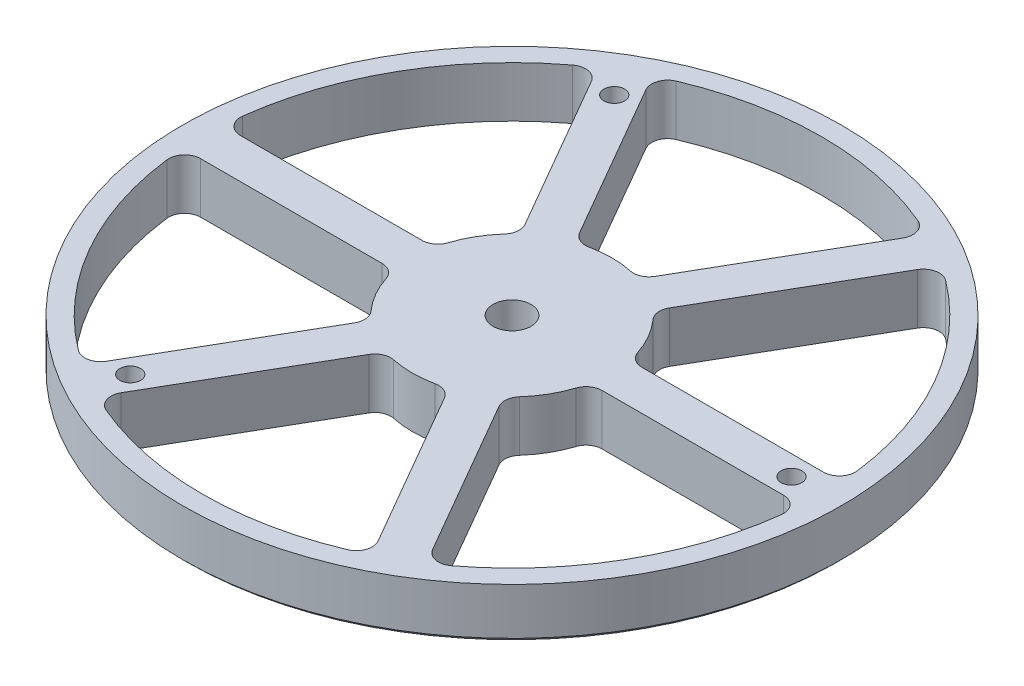
SolidWorks part; units mm, degrees
material "6061-T6 (SS)"
ref_plane "Front Plane" through (0, 0, 0) normal (0, 0, 1) x (1, 0, 0)
ref_plane "Top Plane" through (0, 0, 0) normal (0, 1, 0) x (1, 0, 0)
ref_plane "Right Plane" through (0, 0, 0) normal (1, 0, 0) x (0, 0, -1)
sketch "Sketch2" plane through (0, 0, 0) normal (1, 0, 0) x (0, 0, -1)
  line L0 (0, 0) -> (-82.55, 0)
  line L1 (-82.55, 0) -> (-82.55, 12.7)
  line L2 (-82.55, 12.7) -> (0, 12.7)
  line L5 (0, 12.7) -> (0, 0)
  dimension "D1" = 82.55
  dimension "D2" = 12.7
ref_axis "Axis1" through (0, -0.635, 0) along (0, 1, 0)
revolve "Revolve1" add sketch "Sketch2" angle 360 about axis through (0, -0.635, 0) along (0, 1, 0)
hole_wizard "#6 (0.204) Diameter Hole1" positions "Sketch6" profile "Sketch7" hole size "#6" standard "ANSI Inch" end condition through all
sketch "Sketch6" plane through (0, 12.7, 0) normal (0, 1, 0) x (1, 0, 0)
  line L0 (0, 0) -> (-69.8201, 120.932) construction
  line L2 (0, 0) -> (0, 109.0908) construction
  point P0 (-35, 60.6218)
  dimension "D1" = 30
  dimension "D2" = 70
sketch "Sketch7" plane through (-35, 12.7, -60.6218) normal (1, 0, 0) x (0, 0, 1)
  line L0 (0, 0) -> (0, 12.7)
  line L1 (0, 12.7) -> (2.5908, 12.7)
  line L2 (2.5908, 12.7) -> (2.5908, 0)
  line L5 (2.5908, 0) -> (0, 0)
  line L11 (0, -6.35) -> (0, 107.95) construction
  dimension "Thru Hole Dia." = 5.1816
  dimension "Thru Hole Depth" = 12.7
pattern_circular "CirPattern3" count 3 over 360 about axis through (0, -0.635, 0) along (0, 1, 0) of "#6 (0.204) Diameter Hole1"
sketch "Sketch8" plane through (0, 12.7, 0) normal (0, 1, 0) x (1, 0, 0)
  line L4 (0, 0) -> (0, 93.9995) construction
  line L5 (0, 0) -> (113.8372, 0) construction
  line L6 (-7.9173, 23.7132) -> (-34.3642, 69.5205)
  line L7 (7.9173, 23.7132) -> (34.3642, 69.5205)
  line L8 (0, 0) -> (-35, 60.6218) construction
  arc A0 (-7.9173, 23.7132) -> (7.9173, 23.7132) centre (0, 0) cw
  arc A1 (-34.3642, 69.5205) -> (34.3642, 69.5205) centre (0, 0) cw
  circle A2 centre (0, 0) radius 82.55 construction
  dimension "D1" = 25
  dimension "D2" = 5
  dimension "D3" = 5
extrude "Cut-Extrude1" cut sketch "Sketch8" against normal through all
fillet "Fillet1" radius 4 4 edges at (7.9173, 6.35, -23.7132) (34.3642, 6.35, -69.5205) (-7.9173, 6.35, -23.7132) (-34.3642, 6.35, -69.5205)
pattern_circular "CirPattern4" count 6 over 360 about axis through (0, -0.635, 0) along (0, 1, 0) of "Cut-Extrude1", "Fillet1"
chamfer "Chamfer2" distance 1 angle 45 1 edges at (0, 0, -82.55)
hole_wizard "3/8 (0.375) Diameter Hole1" positions "Sketch9" profile "Sketch11" hole size "3/8" standard "ANSI Inch" end condition through all
sketch "Sketch9" plane through (0, 0, 0) normal (0, -1, 0) x (-1, 0, 0)
  point P0 (0, 0)
sketch "Sketch11" plane through (0, 0, 0) normal (1, 0, 0) x (0, 0, -1)
  line L0 (0, 0) -> (0, 12.7)
  line L1 (0, 12.7) -> (4.7625, 12.7)
  line L2 (4.7625, 12.7) -> (4.7625, 0)
  line L5 (4.7625, 0) -> (0, 0)
  line L11 (0, -6.35) -> (0, 107.95) construction
  dimension "Thru Hole Dia." = 9.525
  dimension "Thru Hole Depth" = 12.7
equation "\"TubeDiameter\" = 6.500in"
equation "\"D1@Sketch2\"=\"TubeDiameter\"/2"
